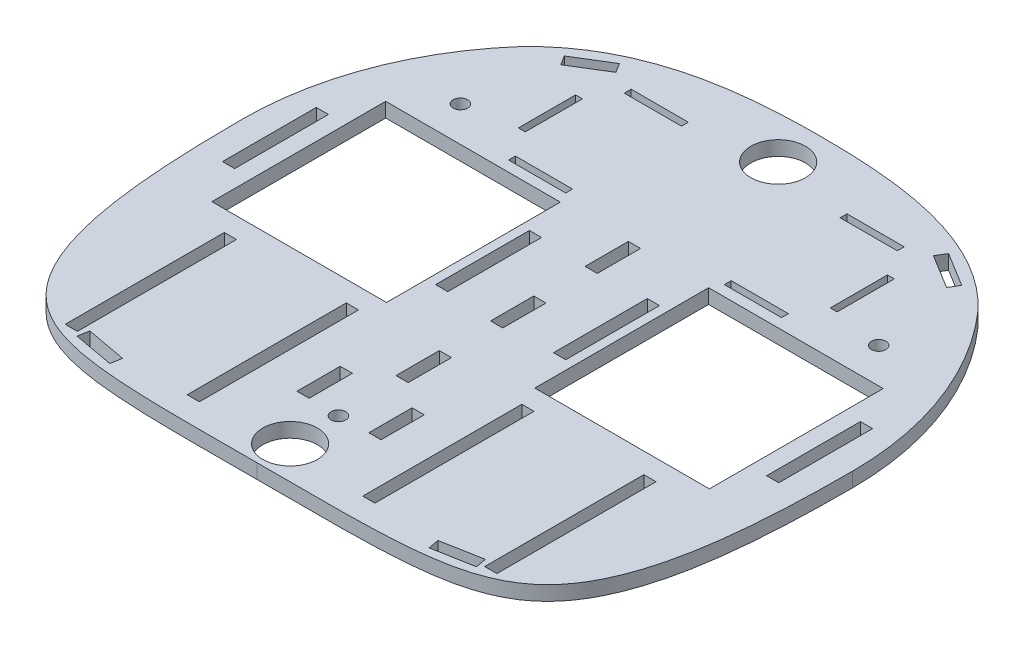
SolidWorks part; units mm, degrees
ref_plane "Front Plane" through (0, 0, 0) normal (0, 0, 1) x (1, 0, 0)
ref_plane "Top Plane" through (0, 0, 0) normal (0, 1, 0) x (1, 0, 0)
ref_plane "Right Plane" through (0, 0, 0) normal (1, 0, 0) x (0, 0, -1)
sketch "Sketch1" plane through (0, 0, 0) normal (0, 1, 0) x (1, 0, 0)
  line L0 (0, 0) -> (-157.9039, -157.9039) construction
  line L1 (0, -127) -> (0, 133.35) construction
  arc A0 (133.35, 0) -> (-133.35, 0) centre (0, 0) ccw
  spline S0 degree 3 poles (-133.35, 0) (-133.35, -51.198) (-123.8034, -129.8051) (-58.428, -127) (0, -127) knots 0 0 0 0 0.502616 1 1 1 1
  spline S1 degree 3 poles (133.35, 0) (133.35, -51.198) (123.8034, -129.8051) (58.428, -127) (0, -127) knots 0 0 0 0 0.502616 1 1 1 1
  dimension "D1" = 266.7
extrude "Base" add sketch "Sketch1" along normal blind 6.35
sketch "ShaftLayout" plane through (0, 6.35, 0) normal (0, 1, 0) x (1, 0, 0)
  line L0 (-133.35, 0) -> (133.35, 0) construction
  line L1 (0, 133.35) -> (0, -127) construction
  line L2 (-114.7053, -6.35) -> (-104.7993, -6.35)
  line L3 (-36.3853, -38) -> (-94.3853, -38)
  line L4 (-36.3853, -38) -> (-36.3853, 38)
  line L5 (-36.3853, 38) -> (-94.3853, 38)
  line L6 (-94.3853, -38) -> (-94.3853, 38)
  line L7 (-36.3853, -38) -> (-94.3853, 38) construction
  line L8 (-36.3853, 38) -> (-94.3853, -38) construction
  line L9 (-102.0053, -15.875) -> (-104.7993, -15.875)
  line L10 (-102.0053, -15.875) -> (-102.0053, 15.875)
  line L11 (-102.0053, 15.875) -> (-104.7993, 15.875)
  line L12 (-104.7993, -15.875) -> (-104.7993, 15.875)
  line L13 (-102.0053, -15.875) -> (-104.7993, 15.875) construction
  line L14 (-102.0053, 15.875) -> (-104.7993, -15.875) construction
  line L15 (-114.7053, -6.35) -> (-114.7053, 6.35)
  line L16 (-104.7993, -6.35) -> (-104.7993, 6.35)
  line L17 (-114.7053, 6.35) -> (-104.7993, 6.35)
  line L18 (-114.7053, -6.35) -> (-104.7993, 6.35) construction
  line L19 (-104.7993, -6.35) -> (-114.7053, 6.35) construction
  line L20 (-116.2928, -9.525) -> (-114.7053, -9.525)
  line L21 (-116.2928, -9.525) -> (-116.2928, 9.525)
  line L22 (-114.7053, -9.525) -> (-114.7053, 9.525)
  line L23 (-116.2928, 9.525) -> (-114.7053, 9.525)
  line L24 (-116.2928, -9.525) -> (-114.7053, 9.525) construction
  line L25 (-114.7053, -9.525) -> (-116.2928, 9.525) construction
  line L26 (-127.4053, -7.9375) -> (-116.2928, -7.9375)
  line L27 (-127.4053, -7.9375) -> (-127.4053, 7.9375)
  line L28 (-116.2928, -7.9375) -> (-116.2928, 7.9375)
  line L29 (-127.4053, 7.9375) -> (-116.2928, 7.9375)
  line L30 (-127.4053, -7.9375) -> (-116.2928, 7.9375) construction
  line L31 (-116.2928, -7.9375) -> (-127.4053, 7.9375) construction
  line L32 (-17.3353, -7.9375) -> (-28.4478, -7.9375)
  line L33 (-30.0353, -9.525) -> (-28.4478, -9.525)
  line L34 (-30.0353, -9.525) -> (-30.0353, 9.525)
  line L35 (-30.0353, 9.525) -> (-28.4478, 9.525)
  line L36 (-28.4478, -9.525) -> (-28.4478, 9.525)
  line L37 (-30.0353, -9.525) -> (-28.4478, 9.525) construction
  line L38 (-30.0353, 9.525) -> (-28.4478, -9.525) construction
  line L39 (-17.3353, -7.9375) -> (-17.3353, 7.9375)
  line L40 (-28.4478, -7.9375) -> (-28.4478, 7.9375)
  line L41 (-17.3353, 7.9375) -> (-28.4478, 7.9375)
  line L42 (-17.3353, -7.9375) -> (-28.4478, 7.9375) construction
  line L43 (-28.4478, -7.9375) -> (-17.3353, 7.9375) construction
  line L45 (-67.3853, -10.033) -> (-56.3853, -10.033)
  line L46 (-67.3853, -10.033) -> (-67.3853, 10.033)
  line L47 (-67.3853, 10.033) -> (-56.3853, 10.033)
  line L48 (-56.3853, -10.033) -> (-56.3853, 10.033)
  line L49 (-67.3853, -10.033) -> (-56.3853, 10.033) construction
  line L50 (-67.3853, 10.033) -> (-56.3853, -10.033) construction
  arc A0 (133.35, 0) -> (-133.35, 0) centre (0, 0) ccw construction
  point P10 (-65.3853, 0)
  point P15 (-103.4023, 0)
  point P20 (-29.2416, 0)
  point P21 (-109.7523, 0)
  point P22 (-115.4991, 0)
  point P23 (-121.8491, 0)
  point P40 (-61.8853, 0)
  point P41 (-22.8916, 0)
  dimension "D1" = 58
  dimension "D2" = 76
  dimension "D3" = 7.62
  dimension "D4" = 2.794
  dimension "D5" = 31.75
  dimension "D6" = 9.906
  dimension "D7" = 12.7
  dimension "D8" = 19.05
  dimension "D9" = 1.5875
  dimension "D10" = 12.7
  dimension "D11" = 15.875
  dimension "D12" = 19.05
  dimension "D13" = 1.5875
  dimension "D14" = 15.875
  dimension "D15" = 12.7
  dimension "D16" = 6.35
  dimension "D17" = 20.066
  dimension "D18" = 20
  dimension "D19" = 11
sketch "MotorLayout" plane through (0, 6.35, 0) normal (0, 1, 0) x (1, 0, 0)
  line L0 (-94.3853, -81.74) -> (-114.3853, -81.74) construction
  line L1 (-94.3853, -110.24) -> (-18.3853, -110.24)
  line L2 (-94.3853, -110.24) -> (-94.3853, -53.24)
  line L3 (-94.3853, -53.24) -> (-18.3853, -53.24)
  line L4 (-18.3853, -110.24) -> (-18.3853, -53.24)
  line L5 (-94.3853, -110.24) -> (-18.3853, -53.24) construction
  line L6 (-94.3853, -53.24) -> (-18.3853, -110.24) construction
  line L7 (-114.7053, -92.0587) -> (-104.7993, -92.0587)
  line L8 (-104.7993, -97.615) -> (-102.0053, -97.615)
  line L9 (-104.7993, -97.615) -> (-104.7993, -65.865)
  line L10 (-104.7993, -65.865) -> (-102.0053, -65.865)
  line L11 (-102.0053, -97.615) -> (-102.0053, -65.865)
  line L12 (-104.7993, -97.615) -> (-102.0053, -65.865) construction
  line L13 (-104.7993, -65.865) -> (-102.0053, -97.615) construction
  line L14 (-36.3853, -38) -> (-94.3853, -38) construction
  line L15 (-114.7053, -92.0587) -> (-114.7053, -71.4212)
  line L16 (-104.7993, -92.0587) -> (-104.7993, -71.4212)
  line L17 (-114.7053, -71.4212) -> (-104.7993, -71.4212)
  line L18 (-114.7053, -92.0587) -> (-104.7993, -71.4212) construction
  line L19 (-104.7993, -92.0587) -> (-114.7053, -71.4212) construction
  line L20 (-103.4023, -1000) -> (-103.4023, 49000) construction
  line L21 (-34.8953, -53.24) -> (-34.8953, -110.24) construction
  point P0 (-56.3853, -81.74)
  point P7 (-103.4023, -81.74)
  point P14 (-109.7523, -81.74)
  dimension "D1" = 20
  dimension "D2" = 76
  dimension "D3" = 57
  dimension "D4" = 2.794
  dimension "D5" = 15.24
  dimension "D6" = 31.75
  dimension "D7" = 20.6375
  dimension "D8" = 12.7
  dimension "D9" = 7.62
  dimension "D10" = 16.51
sketch "Sketch6" plane through (0, 6.35, 0) normal (0, 1, 0) x (1, 0, 0)
  line L0 (-36.3853, -38) -> (-36.3853, 38) construction
  line L1 (-32.4166, -38) -> (-108.7681, -38)
  line L2 (-32.4166, -38) -> (-32.4166, 38)
  line L3 (-32.4166, 38) -> (-108.7681, 38)
  line L4 (-108.7681, -38) -> (-108.7681, 38)
  line L5 (-28.4478, -9.525) -> (-28.4478, 9.525) construction
  line L6 (-104.7993, -15.875) -> (-104.7993, 15.875) construction
  line L7 (0, 133.35) -> (0, -127) construction
  line L8 (28.4478, 20.5105) -> (23.1138, -20.5105) construction
  line L9 (28.4478, -20.5105) -> (23.1138, 20.5105) construction
  line L10 (116.2928, 20.5105) -> (121.6268, -20.5105) construction
  line L11 (116.2928, -20.5105) -> (121.6268, 20.5105) construction
  line L12 (-133.35, 0) -> (133.35, 0) construction
  line L13 (-116.2928, -20.5105) -> (-121.6268, -20.5105)
  line L14 (-116.2928, -20.5105) -> (-116.2928, 20.5105)
  line L15 (-116.2928, 20.5105) -> (-121.6268, 20.5105)
  line L16 (-121.6268, -20.5105) -> (-121.6268, 20.5105)
  line L17 (-116.2928, -20.5105) -> (-121.6268, 20.5105) construction
  line L18 (-116.2928, 20.5105) -> (-121.6268, -20.5105) construction
  line L19 (-116.2928, -9.525) -> (-116.2928, 9.525) construction
  line L20 (-127.4053, 7.9375) -> (-116.2928, 7.9375) construction
  line L21 (-17.3353, 7.9375) -> (-28.4478, 7.9375) construction
  line L22 (-28.4478, -20.5105) -> (-23.1138, -20.5105)
  line L23 (-28.4478, -20.5105) -> (-28.4478, 20.5105)
  line L24 (-28.4478, 20.5105) -> (-23.1138, 20.5105)
  line L25 (-23.1138, -20.5105) -> (-23.1138, 20.5105)
  line L26 (-28.4478, -20.5105) -> (-23.1138, 20.5105) construction
  line L27 (-28.4478, 20.5105) -> (-23.1138, -20.5105) construction
  line L28 (23.1138, -20.5105) -> (23.1138, 20.5105)
  line L29 (28.4478, 20.5105) -> (23.1138, 20.5105)
  line L30 (28.4478, -20.5105) -> (28.4478, 20.5105)
  line L31 (28.4478, -20.5105) -> (23.1138, -20.5105)
  line L32 (121.6268, -20.5105) -> (121.6268, 20.5105)
  line L33 (116.2928, 20.5105) -> (121.6268, 20.5105)
  line L34 (116.2928, -20.5105) -> (116.2928, 20.5105)
  line L35 (116.2928, -20.5105) -> (121.6268, -20.5105)
  line L36 (108.7681, -38) -> (108.7681, 38)
  line L37 (32.4166, 38) -> (108.7681, 38)
  line L38 (32.4166, -38) -> (32.4166, 38)
  line L39 (32.4166, -38) -> (108.7681, -38)
  point P16 (-118.9598, 0)
  point P27 (-25.7808, 0)
  point P44 (25.7808, 0)
  point P45 (118.9598, 0)
  dimension "D1" = 3.9688
  dimension "D2" = 3.9688
  dimension "D3" = 12.573
  dimension "D4" = 12.573
  dimension "D5" = 5.334
  dimension "D6" = 5.334
extrude "WheelShaftCut" cut sketch "Sketch6" against normal through all
sketch "Sketch8" plane through (0, 6.35, 0) normal (0, 1, 0) x (1, 0, 0)
  line L0 (-94.3853, -81.74) -> (-18.3853, -81.74) construction
  line L1 (-18.3853, -110.24) -> (-18.3853, -53.24) construction
  line L2 (-94.3853, -53.24) -> (-18.3853, -53.24) construction
  line L3 (-35.7113, -116.5265) -> (-41.0453, -116.5265)
  line L4 (-35.7113, -116.5265) -> (-35.7113, -46.9535)
  line L5 (-35.7113, -46.9535) -> (-41.0453, -46.9535)
  line L6 (-41.0453, -116.5265) -> (-41.0453, -46.9535)
  line L7 (-35.7113, -116.5265) -> (-41.0453, -46.9535) construction
  line L8 (-35.7113, -46.9535) -> (-41.0453, -116.5265) construction
  line L9 (18.3853, -72.2785) -> (13.0513, -91.2015) construction
  line L10 (18.3853, -91.2015) -> (13.0513, -72.2785) construction
  line L11 (18.3853, -81.74) -> (15.7183, -81.74) construction
  line L12 (89.0513, -46.9535) -> (94.3853, -116.5265) construction
  line L13 (89.0513, -116.5265) -> (94.3853, -46.9535) construction
  line L14 (35.7113, -46.9535) -> (41.0453, -116.5265) construction
  line L15 (-89.0513, -116.5265) -> (-94.3853, -116.5265)
  line L16 (-89.0513, -116.5265) -> (-89.0513, -46.9535)
  line L17 (-89.0513, -46.9535) -> (-94.3853, -46.9535)
  line L18 (-94.3853, -116.5265) -> (-94.3853, -46.9535)
  line L19 (-89.0513, -116.5265) -> (-94.3853, -46.9535) construction
  line L20 (-89.0513, -46.9535) -> (-94.3853, -116.5265) construction
  line L21 (-94.3853, -110.24) -> (-94.3853, -53.24) construction
  line L22 (0, 133.35) -> (0, -127) construction
  line L23 (35.7113, -116.5265) -> (41.0453, -46.9535) construction
  line L24 (94.3853, -81.74) -> (18.3853, -81.74) construction
  line L25 (13.0513, -91.2015) -> (13.0513, -72.2785)
  line L26 (18.3853, -72.2785) -> (13.0513, -72.2785)
  line L27 (18.3853, -91.2015) -> (18.3853, -72.2785)
  line L28 (18.3853, -91.2015) -> (13.0513, -91.2015)
  line L29 (94.3853, -116.5265) -> (94.3853, -46.9535)
  line L30 (89.0513, -46.9535) -> (94.3853, -46.9535)
  line L31 (89.0513, -116.5265) -> (89.0513, -46.9535)
  line L32 (89.0513, -116.5265) -> (94.3853, -116.5265)
  line L33 (41.0453, -116.5265) -> (41.0453, -46.9535)
  line L34 (35.7113, -46.9535) -> (41.0453, -46.9535)
  line L35 (35.7113, -116.5265) -> (35.7113, -46.9535)
  line L36 (35.7113, -116.5265) -> (41.0453, -116.5265)
  line L37 (-94.3853, -110.24) -> (-18.3853, -110.24) construction
  line L42 (-18.3853, -81.74) -> (-15.7183, -81.74) construction
  line L44 (-18.3853, -91.2015) -> (-13.0513, -91.2015)
  line L45 (-18.3853, -91.2015) -> (-18.3853, -72.2785)
  line L46 (-18.3853, -72.2785) -> (-13.0513, -72.2785)
  line L47 (-13.0513, -91.2015) -> (-13.0513, -72.2785)
  line L48 (-18.3853, -91.2015) -> (-13.0513, -72.2785) construction
  line L49 (-18.3853, -72.2785) -> (-13.0513, -91.2015) construction
  point P6 (-63.7079, -81.74)
  point P7 (-38.2513, -81.74)
  point P19 (-91.5913, -81.74)
  point P39 (91.5913, -81.74)
  point P40 (38.2513, -81.74)
  dimension "D1" = 5.334
  dimension "D2" = 6.2865
  dimension "D4" = 5.334
  dimension "D5" = 18.923
  dimension "D6" = 6.2865
  dimension "D3" = 2
extrude "MotorCut" cut sketch "Sketch8" against normal through all
sketch "BatteryLayout" plane through (0, 6.35, 0) normal (0, 1, 0) x (1, 0, 0)
  line L0 (0, 133.35) -> (0, -127) construction
  line L1 (-32.4166, 38) -> (-108.7681, 38) construction
  line L2 (-66.675, 45.62) -> (66.675, 45.62)
  line L3 (-66.675, 45.62) -> (-66.675, 93.245)
  line L4 (-66.675, 93.245) -> (66.675, 93.245)
  line L5 (66.675, 45.62) -> (66.675, 93.245)
  line L6 (-66.675, 45.62) -> (66.675, 93.245) construction
  line L7 (-66.675, 93.245) -> (66.675, 45.62) construction
  arc A0 (133.35, 0) -> (-133.35, 0) centre (0, 0) ccw construction
  point P6 (0, 69.4325)
  dimension "D1" = 133.35
  dimension "D2" = 47.625
  dimension "D3" = 7.62
sketch "Sketch10" plane through (0, 6.35, 0) normal (0, 1, 0) x (1, 0, 0)
  line L0 (-66.675, 93.245) -> (66.675, 93.245) construction
  line L1 (-59.69, 42.62) -> (-34.69, 42.62)
  line L2 (-59.69, 42.62) -> (-59.69, 45.62)
  line L3 (-59.69, 45.62) -> (-34.69, 45.62)
  line L4 (-34.69, 42.62) -> (-34.69, 45.62)
  line L5 (-59.69, 42.62) -> (-34.69, 45.62) construction
  line L6 (-59.69, 45.62) -> (-34.69, 42.62) construction
  line L7 (-59.69, 96.245) -> (-34.69, 96.245)
  line L8 (-59.69, 96.245) -> (-59.69, 93.245)
  line L9 (-59.69, 93.245) -> (-34.69, 93.245)
  line L10 (-34.69, 96.245) -> (-34.69, 93.245)
  line L11 (-59.69, 96.245) -> (-34.69, 93.245) construction
  line L12 (-59.69, 93.245) -> (-34.69, 96.245) construction
  line L13 (-66.675, 45.62) -> (66.675, 45.62) construction
  line L14 (-66.675, 45.62) -> (-66.675, 93.245) construction
  line L15 (0, 69.4325) -> (-66.675, 69.4325) construction
  line L16 (-66.675, 56.9325) -> (-69.675, 56.9325)
  line L17 (-66.675, 56.9325) -> (-66.675, 81.9325)
  line L18 (-66.675, 81.9325) -> (-69.675, 81.9325)
  line L19 (-69.675, 56.9325) -> (-69.675, 81.9325)
  line L20 (0, 133.35) -> (0, -127) construction
  line L21 (59.69, 93.245) -> (34.69, 96.245) construction
  line L22 (59.69, 96.245) -> (34.69, 93.245) construction
  line L23 (59.69, 45.62) -> (34.69, 42.62) construction
  line L24 (59.69, 42.62) -> (34.69, 45.62) construction
  line L25 (69.675, 56.9325) -> (69.675, 81.9325)
  line L26 (66.675, 81.9325) -> (69.675, 81.9325)
  line L27 (66.675, 56.9325) -> (66.675, 81.9325)
  line L28 (66.675, 56.9325) -> (69.675, 56.9325)
  line L29 (34.69, 96.245) -> (34.69, 93.245)
  line L30 (59.69, 93.245) -> (34.69, 93.245)
  line L31 (59.69, 96.245) -> (59.69, 93.245)
  line L32 (59.69, 96.245) -> (34.69, 96.245)
  line L33 (34.69, 42.62) -> (34.69, 45.62)
  line L34 (59.69, 45.62) -> (34.69, 45.62)
  line L35 (59.69, 42.62) -> (59.69, 45.62)
  line L36 (59.69, 42.62) -> (34.69, 42.62)
  point P0 (-47.19, 44.12)
  point P5 (-47.19, 94.745)
  point P20 (-66.675, 69.4325)
  point P40 (66.675, 69.4325)
  point P41 (47.19, 94.745)
  point P42 (47.19, 44.12)
  dimension "D1" = 3
  dimension "D2" = 3
  dimension "D3" = 25
  dimension "D4" = 25
  dimension "D5" = 6.985
  dimension "D6" = 6.985
  dimension "D7" = 3
  dimension "D8" = 25
extrude "VelcroCut" cut sketch "Sketch10" against normal through all
sketch "Sketch11" plane through (0, 6.35, 0) normal (0, 1, 0) x (1, 0, 0)
  line L0 (0, 133.35) -> (0, -127) construction
  line L1 (-133.35, 0) -> (133.35, 0) construction
  circle A1 centre (0, -91.44) radius 3.175
  circle A2 centre (-91.44, 53.34) radius 3.175
  circle A3 centre (91.44, 53.34) radius 3.175
  dimension "D1" = 6.35
  dimension "D2" = 53.34
  dimension "D3" = 6.35
  dimension "D6" = 91.44
  dimension "D4" = 91.44
extrude "ScrewCut" cut sketch "Sketch11" against normal through all
sketch "Sketch13" plane through (0, 6.35, 0) normal (0, 1, 0) x (1, 0, 0)
  line L0 (0, 133.35) -> (0, -127) construction
  line L1 (-2.667, 19.077) -> (2.667, 19.077)
  line L2 (-2.667, 19.077) -> (-2.667, 38)
  line L3 (-2.667, 38) -> (2.667, 38)
  line L4 (2.667, 19.077) -> (2.667, 38)
  line L5 (-2.667, 19.077) -> (2.667, 38) construction
  line L6 (-2.667, 38) -> (2.667, 19.077) construction
  line L7 (108.7681, 38) -> (32.4166, 38) construction
  line L8 (-2.667, -22.2615) -> (2.667, -22.2615)
  line L9 (-2.667, -22.2615) -> (-2.667, -3.3385)
  line L10 (-2.667, -3.3385) -> (2.667, -3.3385)
  line L11 (2.667, -22.2615) -> (2.667, -3.3385)
  line L12 (-2.667, -22.2615) -> (2.667, -3.3385) construction
  line L13 (-2.667, -3.3385) -> (2.667, -22.2615) construction
  line L14 (-2.667, -63.6) -> (2.667, -63.6)
  line L15 (-2.667, -63.6) -> (-2.667, -44.677)
  line L16 (-2.667, -44.677) -> (2.667, -44.677)
  line L17 (2.667, -63.6) -> (2.667, -44.677)
  line L18 (-2.667, -63.6) -> (2.667, -44.677) construction
  line L19 (-2.667, -44.677) -> (2.667, -63.6) construction
  point P0 (0, 28.5385)
  point P9 (0, 0)
  point P10 (0, -12.8)
  point P15 (0, -54.1385)
  dimension "D1" = 5.334
  dimension "D2" = 18.923
  dimension "D3" = 0
  dimension "D5" = 101.6
  dimension "D4" = 3
extrude "SupportStrutCut" cut sketch "Sketch13" against normal through all
sketch "Sketch16" plane through (0, 6.35, 0) normal (0, 1, 0) x (1, 0, 0)
  line L0 (0, -1000) -> (0, 49000) construction
  line L1 (-100.0331, 133.35) -> (-100.0331, 88.1793)
  line L2 (-100.0331, 133.35) -> (100.0331, 133.35)
  line L3 (100.0331, 133.35) -> (100.0331, 88.1793)
  arc A0 (133.35, 0) -> (-133.35, 0) centre (0, 0) ccw construction
  spline S0 degree 3 poles (-100.0331, 88.1793) (-73.9195, 115.9102) (-34.9729, 119.8228) (0, 119.8228) knots 0 0 0 0 1 1 1 1
  spline S1 degree 3 poles (100.0331, 88.1793) (73.9195, 115.9102) (34.9729, 119.8228) (0, 119.8228) knots 0 0 0 0 1 1 1 1
extrude "EmptySpaceTrim" cut sketch "Sketch16" against normal through all
sketch "Sketch15" plane through (0, 6.35, 0) normal (0, 1, 0) x (1, 0, 0)
  line L0 (-78.1477, -1116.59) -> (-78.1477, 48883.41) construction
  line L2 (-87.3468, -118.3963) -> (-69.8208, -121.6168)
  line L3 (-87.3468, -118.3963) -> (-86.4746, -113.6498)
  line L4 (-69.8208, -121.6168) -> (-68.9486, -116.8703)
  line L5 (-86.4746, -113.6498) -> (-68.9486, -116.8703)
  line L6 (-87.3468, -118.3963) -> (-68.9486, -116.8703) construction
  line L7 (-69.8208, -121.6168) -> (-86.4746, -113.6498) construction
  line L8 (-84.3532, 90.1176) -> (-69.4173, 99.287)
  line L9 (-84.3532, 90.1176) -> (-86.8782, 94.2303)
  line L10 (-69.4173, 99.287) -> (-71.9422, 103.3998)
  line L11 (-86.8782, 94.2303) -> (-71.9422, 103.3998)
  line L12 (-84.3532, 90.1176) -> (-71.9422, 103.3998) construction
  line L13 (-69.4173, 99.287) -> (-86.8782, 94.2303) construction
  line L14 (0, -1000) -> (0, 49000) construction
  line L15 (69.4173, 99.287) -> (86.8782, 94.2303) construction
  line L16 (84.3532, 90.1176) -> (71.9422, 103.3998) construction
  line L17 (69.8208, -121.6168) -> (86.4746, -113.6498) construction
  line L18 (87.3468, -118.3963) -> (68.9486, -116.8703) construction
  line L19 (88.7973, -116.59) -> (66.5019, -116.59) construction
  line L20 (86.8782, 94.2303) -> (71.9422, 103.3998)
  line L21 (69.4173, 99.287) -> (71.9422, 103.3998)
  line L22 (84.3532, 90.1176) -> (86.8782, 94.2303)
  line L23 (84.3532, 90.1176) -> (69.4173, 99.287)
  line L24 (86.4746, -113.6498) -> (68.9486, -116.8703)
  line L25 (69.8208, -121.6168) -> (68.9486, -116.8703)
  line L26 (87.3468, -118.3963) -> (86.4746, -113.6498)
  line L27 (87.3468, -118.3963) -> (69.8208, -121.6168)
  point P4 (-78.1477, 96.7587)
  point P7 (-78.1477, -117.6333)
  point P30 (78.1477, -117.6333)
  point P31 (78.1477, 96.7587)
  dimension "D1" = 4.826
  dimension "D2" = 17.526
  dimension "D3" = 17.526
  dimension "D4" = 4.826
extrude "TapeSensorCut" cut sketch "Sketch15" against normal through all
sketch "Sketch17" plane through (0, 6.35, 0) normal (0, 1, 0) x (1, 0, 0)
  line L0 (0, -1000) -> (0, 49000) construction
  line L1 (-34.69, 93.245) -> (34.69, 93.245) construction
  circle A0 centre (0, 100.8346) radius 11.938
  circle A1 centre (0, 100.8346) radius 5 construction
  circle A2 centre (0, -112.5625) radius 11.938
  dimension "D1" = 23.876
  dimension "D2" = 10
  dimension "D3" = 23.876
extrude "CasterCut" cut sketch "Sketch17" against normal through all
sketch "Layer1Limits" plane through (0, 0, 0) normal (0, 1, 0) x (1, 0, 0)
  line L0 (-127, 119.8228) -> (127, -134.1772) construction
  line L1 (-127, -134.1772) -> (127, -134.1772) construction
  line L2 (-127, -134.1772) -> (-127, 119.8228) construction
  line L3 (-127, 119.8228) -> (127, 119.8228) construction
  line L4 (127, -134.1772) -> (127, 119.8228) construction
  line L5 (127, 119.8228) -> (-127, -134.1772) construction
  line L6 (0, -1000) -> (0, 49000) construction
  point P4 (0, -7.1772)
  dimension "D1" = 254
  dimension "D2" = 254
